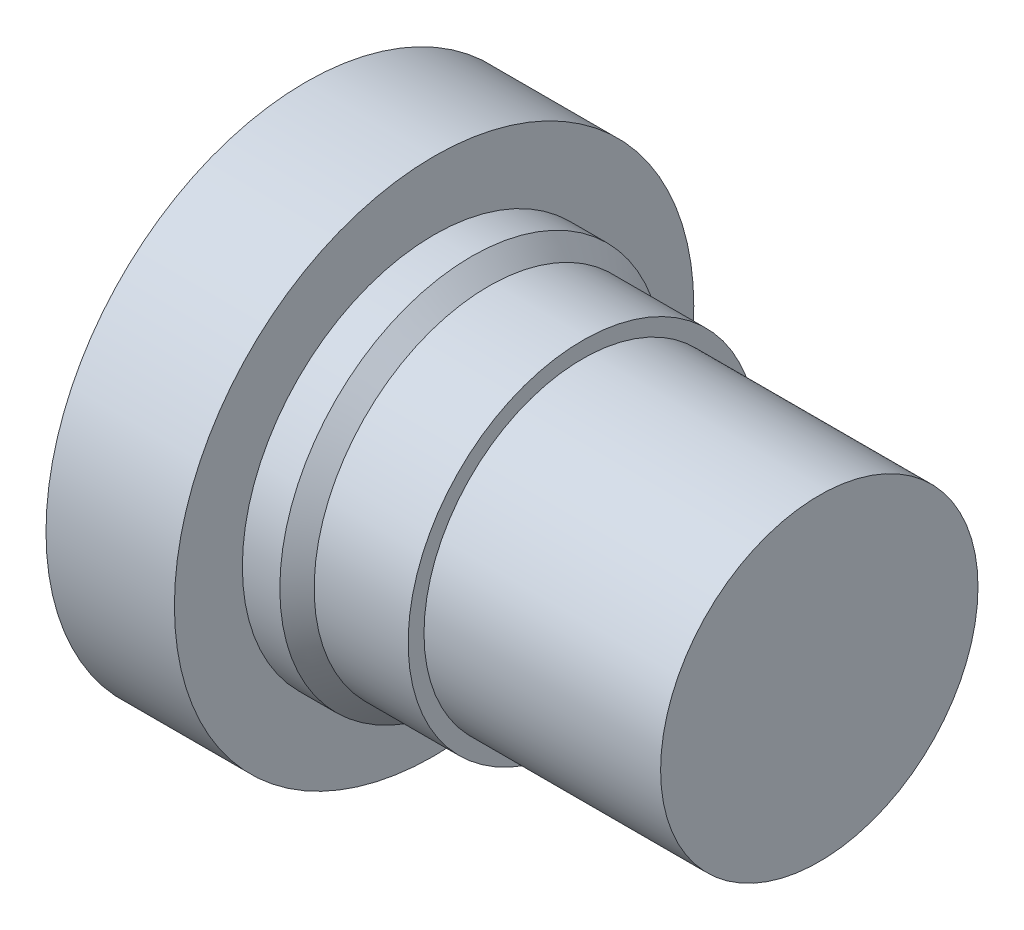
SolidWorks part; units mm, degrees
ref_plane "Front Plane" through (0, 0, 0) normal (0, 0, 1) x (1, 0, 0)
ref_plane "Top Plane" through (0, 0, 0) normal (0, 1, 0) x (1, 0, 0)
ref_plane "Right Plane" through (0, 0, 0) normal (1, 0, 0) x (0, 0, -1)
sketch "Sketch1" plane through (0, 0, 0) normal (0, 0, 1) x (1, 0, 0)
  line L0 (0, 0) -> (0, 9)
  line L1 (0, 9) -> (4.45, 9)
  line L2 (4.45, 9) -> (4.45, 6.6452)
  line L3 (4.45, 6.6452) -> (5.7486, 6.6452)
  line L4 (5.7486, 6.6452) -> (6.3438, 6.05)
  line L5 (6.3438, 6.05) -> (9.6, 6.05)
  line L6 (9.6, 6.05) -> (9.6, 5.5)
  line L7 (9.6, 5.5) -> (17.8, 5.5)
  line L8 (17.8, 5.5) -> (17.8, 0)
  line L9 (17.8, 0) -> (0, 0)
  dimension "D1" = 9
  dimension "D2" = 4.45
  dimension "D3" = 8.2
  dimension "D4" = 6.05
  dimension "D5" = 5.5
  dimension "D6" = 17.8
revolve "Revolve1" add sketch "Sketch1" angle 360 about L9
sketch "Sketch2" plane through (0, 0, 0) normal (-1, 0, 0) x (0, 0, 1)
  circle A0 centre (0, 0) radius 7
  dimension "D1" = 14
extrude "Cut-Extrude1" cut sketch "Sketch2" against normal blind 0.0001
dome "Dome1" faces to dome 1 distance 1.4 reverse direction no elliptical dome yes face at (0.0001, 0, 7) parameters "D1"=1.4
